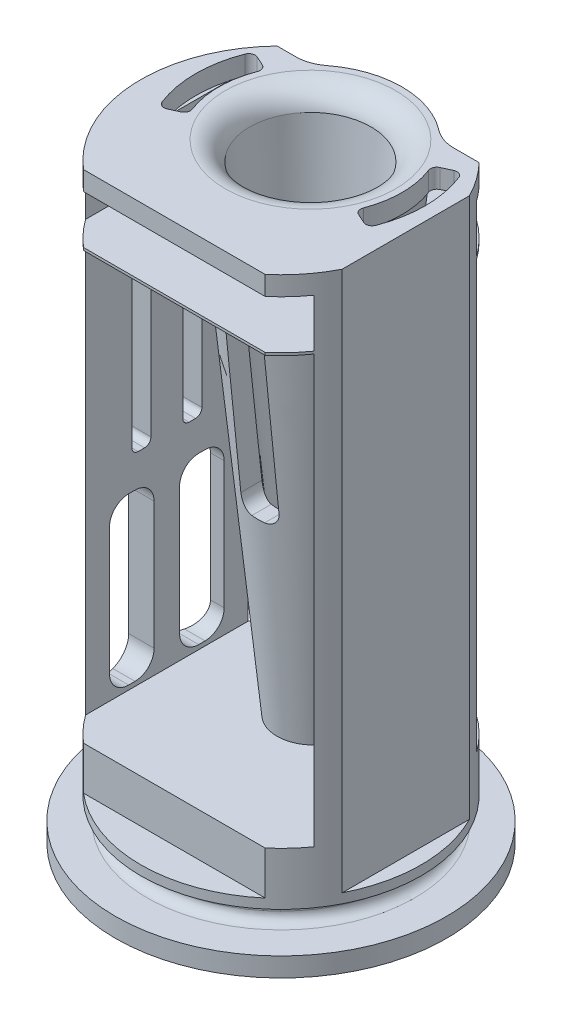
SolidWorks part; units mm, degrees
other "Детальный элемент1"
material "PP Кополимер"
ref_plane "Front Plane" through (0, 0, 0) normal (0, 0, 1) x (1, 0, 0)
ref_plane "Top Plane" through (0, 0, 0) normal (0, 1, 0) x (1, 0, 0)
ref_plane "Right Plane" through (0, 0, 0) normal (1, 0, 0) x (0, 0, -1)
sketch "Эскиз1" plane through (0, 0, 0) normal (0, 1, 0) x (1, 0, 0)
  line L0 (19.6, 9.992) -> (19.6, -9.992)
  line L1 (-14.2632, -16.75) -> (14.2632, -16.75)
  line L2 (-15.8568, 15.25) -> (-12.9239, 15.25)
  line L3 (11.9239, 15.25) -> (15.8568, 15.25)
  line L4 (-0.5, 5.125) -> (-0.5, 23.5612) construction
  line L5 (-0.5, 5.125) -> (-16.8682, 12.625) construction
  line L6 (-14.4479, 11.516) -> (-15.9323, 12.1962)
  line L7 (-14.4479, -1.266) -> (-15.9323, -1.9462)
  line L8 (-0.5, 5.125) -> (-16.8682, -2.375) construction
  line L9 (13.4479, 11.516) -> (14.9323, 12.1962)
  line L10 (13.4479, -1.266) -> (14.9323, -1.9462)
  arc A0 (19.6, 9.992) -> (15.8568, 15.25) centre (0, 0) ccw
  circle A1 centre (-0.5, 5.125) radius 9.5
  arc A2 (8.3046, 16.4881) -> (-9.3046, 16.4881) centre (-0.5, 5.125) ccw
  arc A3 (14.2632, -16.75) -> (19.6, -9.992) centre (0, 0) ccw
  arc A4 (-15.8568, 15.25) -> (-14.2632, -16.75) centre (0, 0) ccw
  arc A5 (-12.9239, 15.25) -> (-9.3046, 16.4881) centre (-12.9239, 21.1592) ccw
  arc A6 (11.9239, 15.25) -> (8.3046, 16.4881) centre (11.9239, 21.1592) cw
  arc A7 (8.3046, 16.4881) -> (-9.3046, 16.4881) centre (-0.5, 5.125) ccw
  arc A9 (-13.9302, 10.2504) -> (-13.9302, -0.0004) centre (-0.5, 5.125) ccw
  arc A10 (-17.2809, 11.6494) -> (-17.2809, -1.3994) centre (-0.5, 5.125) ccw
  arc A11 (-15.9323, -1.9462) -> (-17.2809, -1.3994) centre (-16.3489, -1.0371) cw
  arc A12 (-13.9302, -0.0004) -> (-14.4479, -1.266) centre (-14.8645, -0.3569) cw
  arc A13 (-14.4479, 11.516) -> (-13.9302, 10.2504) centre (-14.8645, 10.6069) cw
  arc A14 (-17.2809, 11.6494) -> (-15.9323, 12.1962) centre (-16.3489, 11.2871) cw
  arc A15 (13.4479, 11.516) -> (12.9302, 10.2504) centre (13.8645, 10.6069) ccw
  arc A16 (16.2809, 11.6494) -> (14.9323, 12.1962) centre (15.3489, 11.2871) ccw
  arc A17 (12.9302, -0.0004) -> (13.4479, -1.266) centre (13.8645, -0.3569) ccw
  arc A18 (14.9323, -1.9462) -> (16.2809, -1.3994) centre (15.3489, -1.0371) ccw
  arc A19 (12.9302, 10.2504) -> (12.9302, -0.0004) centre (-0.5, 5.125) cw
  arc A20 (16.2809, 11.6494) -> (16.2809, -1.3994) centre (-0.5, 5.125) cw
  point P6 (-18.5046, 5.125)
  point P28 (-13.5684, -0.863)
  point P31 (-13.5684, 11.113)
  dimension "D1" = 44
  dimension "D3" = 19
  dimension "D5" = 28.75
  dimension "D9" = 15
  dimension "D10" = 1
  dimension "D2" = 41.6
  dimension "D4" = 10.6
  dimension "D6" = 38.75
  dimension "D7" = 36.25
  dimension "D8" = 32
extrude "основание" add sketch "Эскиз1" along normal blind 3 contours L3 A6 A2 A5 L2 A4 L1 A3 L0 A0 A1 A10 A14 L6 A13 A9 A12 L7 A11 A16 A20 A18 L10 A17 A19 A15 L9 region at (19.0482, 0, 0)
sketch "Эскиз2" plane through (0, 0, 0) normal (0, 1, 0) x (1, 0, 0)
  line L0 (19.6, 9.992) -> (19.6, -9.992) construction
  line L1 (-17.9223, -12.759) -> (17.9223, -12.759) construction
  line L2 (-17.9223, -12.759) -> (-17.9223, 12.759)
  line L3 (-17.9223, 12.759) -> (17.9223, 12.759) construction
  line L4 (17.9223, -12.759) -> (17.9223, 12.759)
  line L5 (-17.9223, -12.759) -> (17.9223, 12.759) construction
  line L6 (-17.9223, 12.759) -> (17.9223, -12.759) construction
  line L7 (19.6, 9.992) -> (19.6, -9.992)
  arc A0 (19.6, 9.992) -> (15.8568, 15.25) centre (0, 0) ccw construction
  arc A1 (-15.8568, 15.25) -> (-14.2632, -16.75) centre (0, 0) ccw construction
  arc A2 (-17.9223, 12.759) -> (-17.9223, -12.759) centre (0, 0) ccw
  arc A3 (14.2632, -16.75) -> (19.6, -9.992) centre (0, 0) ccw construction
  arc A4 (17.9223, -12.759) -> (19.6, -9.992) centre (0, 0) ccw
  arc A5 (19.6, 9.992) -> (17.9223, 12.759) centre (0, 0) ccw
  point P0 (0, 0)
  dimension "D1" = 35.8445
extrude "боковые ребра" add sketch "Эскиз2" against normal blind 75
sketch "Эскиз3" plane through (0, -75, 0) normal (0, -1, 0) x (-1, 0, 0)
  line L0 (14.2632, -16.75) -> (-14.2632, -16.75)
  line L1 (14.2632, -16.75) -> (-14.2632, -16.75) construction
  line L3 (15.8568, 15.25) -> (-7.5223, 20.674)
  line L4 (-19.6, 9.992) -> (-19.6, -9.992)
  line L5 (-19.6, -9.992) -> (-19.6, 9.992) construction
  arc A0 (-7.5223, 20.674) -> (-19.6, 9.992) centre (0, 0) ccw
  arc A1 (-14.2632, -16.75) -> (15.8568, 15.25) centre (0, 0) ccw
  arc A5 (-19.6, -9.992) -> (-14.2632, -16.75) centre (0, 0) ccw
  arc M2 (17.9223, -12.759) -> (17.9223, 12.759) centre (0, 0) ccw
  line M3 (17.9223, 12.759) -> (17.9223, -12.759)
  dimension "D1" = 24
extrude "примыкание ручки" add sketch "Эскиз3" along normal blind 2.8 contours L0 A1 L3 A0 M3 | M3 M2 region at (0.7797, -75, -0.6462) region at (-19.5671, -75, 0)
sketch "Эскиз4" plane through (-17.9223, 0, 0) normal (1, 0, 0) x (0, 0, -1)
  line L0 (0, 0) -> (0, -77.8) construction
  line L1 (2, -51.3) -> (2, -71.3)
  line L2 (-16.75, -77.8) -> (15.25, -77.8) construction
  line L3 (6, -74.3) -> (5, -74.3)
  line L4 (9, -71.3) -> (9, -51.3)
  line L5 (6, -48.3) -> (5, -48.3)
  line L6 (-9, -71.3) -> (-9, -51.3)
  line L7 (9, -74.3) -> (-9, -48.3) construction
  line L8 (9, -48.3) -> (-9, -74.3) construction
  line L14 (9.992, -77.8) -> (-9.992, -77.8) construction
  line L15 (5.5, -43.3) -> (2.5, -8.3) construction
  line L21 (-4.5, -8.3) -> (-3.5, -8.3)
  line L22 (-5.5, -9.3) -> (-5.5, -42.3)
  line L45 (-4.5, -43.3) -> (-3.5, -43.3)
  line L46 (-2.5, -9.3) -> (-2.5, -42.3)
  line L47 (-5.5, -8.3) -> (-2.5, -43.3) construction
  line L48 (-5.5, -43.3) -> (-2.5, -8.3) construction
  line L65 (5.5, -8.3) -> (2.5, -43.3) construction
  line L66 (2.5, -9.3) -> (2.5, -42.3)
  line L67 (4.5, -43.3) -> (3.5, -43.3)
  line L68 (5.5, -9.3) -> (5.5, -42.3)
  line L85 (4.5, -8.3) -> (3.5, -8.3)
  line L86 (-2, -51.3) -> (-2, -71.3)
  line L87 (-5, -48.3) -> (-6, -48.3)
  line L88 (-5, -74.3) -> (-6, -74.3)
  arc A0 (6, -74.3) -> (9, -71.3) centre (6, -71.3) ccw
  arc A1 (-6, -74.3) -> (-9, -71.3) centre (-6, -71.3) cw
  arc A2 (-6, -48.3) -> (-9, -51.3) centre (-6, -51.3) ccw
  arc A3 (9, -51.3) -> (6, -48.3) centre (6, -51.3) ccw
  arc A4 (-3.5, -43.3) -> (-2.5, -42.3) centre (-3.5, -42.3) ccw
  arc A5 (-4.5, -43.3) -> (-5.5, -42.3) centre (-4.5, -42.3) cw
  arc A6 (-3.5, -8.3) -> (-2.5, -9.3) centre (-3.5, -9.3) cw
  arc A7 (-4.5, -8.3) -> (-5.5, -9.3) centre (-4.5, -9.3) ccw
  arc A8 (4.5, -8.3) -> (5.5, -9.3) centre (4.5, -9.3) cw
  arc A9 (3.5, -8.3) -> (2.5, -9.3) centre (3.5, -9.3) ccw
  arc A10 (4.5, -43.3) -> (5.5, -42.3) centre (4.5, -42.3) ccw
  arc A11 (3.5, -43.3) -> (2.5, -42.3) centre (3.5, -42.3) cw
  arc A12 (5, -74.3) -> (2, -71.3) centre (5, -71.3) cw
  arc A13 (5, -48.3) -> (2, -51.3) centre (5, -51.3) ccw
  arc A14 (-5, -74.3) -> (-2, -71.3) centre (-5, -71.3) ccw
  arc A15 (-5, -48.3) -> (-2, -51.3) centre (-5, -51.3) cw
  point P5 (0, -61.3)
  point P28 (-4, -25.8)
  point P57 (4, -25.8)
  dimension "D4" = 3
  dimension "D8" = 1
  dimension "D11" = 3
  dimension "D1" = 18
  dimension "D2" = 26
  dimension "D3" = 3.5
  dimension "D5" = 5
  dimension "D6" = 5
  dimension "D7" = 3
  dimension "D9" = 35
  dimension "D10" = 4
extrude "перфорация боковых стенок" cut sketch "Эскиз4" against normal through all
sketch "Эскиз6" plane through (0, 0, 0) normal (0, -1, 0) x (-1, 0, 0)
  point P0 (0.5, 5.125)
ref_plane "Плоскость1" through (0, 0, -5.125) normal (0, 0, -1) x (-1, 0, 0)
sketch "Эскиз7" plane through (0, 0, -5.125) normal (0, 0, -1) x (-1, 0, 0)
  line L0 (0, 0) -> (0, -75) construction
  line L1 (15.8568, -75) -> (-7.5223, -75) construction
  line L2 (2.736, -75) -> (10, 0)
  line L3 (-8.3046, 0) -> (9.3046, 0) construction
  line L4 (10, 0) -> (13.014, 0)
  line L6 (13.014, 0) -> (5.75, -75)
  line L7 (5.75, -75) -> (2.736, -75)
  line L9 (-9, 0) -> (10, 0) construction
  dimension "D1" = 11.5
  dimension "D2" = 3
revolve "внутрении конус" add sketch "Эскиз7" angle 360 about L0
sketch "Эскиз8" plane through (0, 0, -5.125) normal (0, 0, -1) x (-1, 0, 0)
  line L0 (-3, -12) -> (-3, -42)
  line L2 (-8.3046, 0) -> (9.3046, 0) construction
  line L3 (-1, -10) -> (1, -10)
  line L7 (3, -12) -> (3, -42)
  line L23 (-1, -44) -> (1, -44)
  arc A0 (1, -44) -> (3, -42) centre (1, -42) ccw
  arc A1 (-3, -42) -> (-1, -44) centre (-1, -42) ccw
  arc A2 (-1, -10) -> (-3, -12) centre (-1, -12) ccw
  arc A3 (1, -10) -> (3, -12) centre (1, -12) cw
  point P5 (0, -13)
  dimension "D1" = 2
  dimension "D2" = 10
extrude "перфорация конуса" cut sketch "Эскиз8" against normal through all both and the other way through all
fillet "Скруг основ конуса" radius 4 1 edges at (-0.5, 3, 4.375)
sketch "Эскиз9" plane through (0, -77.8, 0) normal (0, -1, 0) x (1, 0, 0)
  line L3 (19.6, -9.992) -> (19.6, 9.992)
  line L4 (14.2632, 16.75) -> (-14.2632, 16.75)
  line L5 (-15.8568, -15.25) -> (7.5223, -20.674)
  line L6 (19.6, -9.992) -> (19.6, 9.992)
  line L7 (14.2632, 16.75) -> (-14.2632, 16.75)
  line L8 (-15.8568, -15.25) -> (7.5223, -20.674)
  circle A0 centre (0, 0) radius 14.4801
  arc A4 (19.6, 9.992) -> (14.2632, 16.75) centre (0, 0) ccw
  arc A5 (-14.2632, 16.75) -> (-15.8568, -15.25) centre (0, 0) ccw
  arc A6 (7.5223, -20.674) -> (19.6, -9.992) centre (0, 0) ccw
  arc A7 (19.6, 9.992) -> (14.2632, 16.75) centre (0, 0) ccw
  arc A8 (-14.2632, 16.75) -> (-15.8568, -15.25) centre (0, 0) ccw
  arc A9 (7.5223, -20.674) -> (19.6, -9.992) centre (0, 0) ccw
  line M1 (19.6, -9.992) -> (19.6, 9.992)
  arc M2 (19.6, 9.992) -> (14.2632, 16.75) centre (0, 0) ccw
  line M3 (14.2632, 16.75) -> (-14.2632, 16.75)
  arc M4 (-14.2632, 16.75) -> (-15.8568, -15.25) centre (0, 0) ccw
  line M5 (-15.8568, -15.25) -> (7.5223, -20.674)
  arc M6 (7.5223, -20.674) -> (19.6, -9.992) centre (0, 0) ccw
  dimension "D1" = 0
extrude "шейка ручки" add sketch "Эскиз9" along normal blind 4 contours A0 | A0 M6 M1 M2 M3 M4 M5 region at (14.2043, -77.8, -16.0602) region at (0, -77.8, 0)
sketch "Эскиз10" plane through (0, -81.8, 0) normal (0, -1, 0) x (1, 0, 0)
  circle A0 centre (0, 0) radius 22
  dimension "D1" = 44
extrude "бортик перед прокладкой" add sketch "Эскиз10" along normal blind 1.5
sketch "Эскиз11" plane through (0, -83.3, 0) normal (0, -1, 0) x (1, 0, 0)
  circle A0 centre (0, 0) radius 19.5
  dimension "D1" = 39
extrude "прокладка паз" add sketch "Эскиз11" along normal blind 3.5
sketch "Эскиз12" plane through (0, -86.8, 0) normal (0, -1, 0) x (-1, 0, 0)
  circle A0 centre (0, 0) radius 26
  dimension "D1" = 52
extrude "бортик после прокладки" add sketch "Эскиз12" along normal blind 3
sketch "Эскиз13" plane through (0, -89.8, 0) normal (0, -1, 0) x (1, 0, 0)
  circle A0 centre (0, 0) radius 14
  dimension "D1" = 28
extrude "вырез под внеш ручку" cut sketch "Эскиз13" against normal blind 12
sketch "Эскиз15" plane through (0, -89.8, 0) normal (0, -1, 0) x (1, 0, 0)
  circle A0 centre (0, 0) radius 19
  dimension "D1" = 38
extrude "Вырез-Вытянуть1" [suppressed] cut sketch "Эскиз15" against normal blind 2
sketch "Эскиз16" plane through (0, -89.8, 0) normal (0, -1, 0) x (1, 0, 0)
  circle A0 centre (0, 0) radius 16
  circle A1 centre (0, 0) radius 13
  dimension "D1" = 32
  dimension "D2" = 26
extrude "выступ под упор винтовой крышки" add sketch "Эскиз16" against normal blind 3
fillet "Скругление4" radius 1.5 2 edges at (0, -83.3, -19.5) (0, -86.8, -19.5)
fillet "Скругление3" [suppressed] radius 2
chamfer "Фаска3" [suppressed] distance 4 angle 45
ref_plane "Плоскость2" through (0, -8, 0) normal (0, -1, 0) x (-1, 0, 0)
sketch "Эскиз17" plane through (0, -8, 0) normal (0, -1, 0) x (-1, 0, 0)
  line L0 (-17.9223, 12.759) -> (-17.9223, -12.759)
  line L1 (-14.2632, -16.75) -> (14.2632, -16.75)
  line L2 (17.9223, -12.759) -> (17.9223, 12.759)
  line L3 (15.8568, 15.25) -> (-7.5223, 20.674)
  arc A0 (-17.9223, 12.759) -> (-7.5223, 20.674) centre (0, 0) cw
  arc A1 (-17.9223, -12.759) -> (-14.2632, -16.75) centre (0, 0) ccw
  arc A2 (14.2632, -16.75) -> (17.9223, -12.759) centre (0, 0) ccw
  circle A3 centre (0, 5.125) radius 12.0139
  arc A4 (17.9223, 12.759) -> (15.8568, 15.25) centre (0, 0) ccw
extrude "Бобышка-Вытянуть2" add sketch "Эскиз17" against normal blind 0.4
chamfer "фаска под ручку " [suppressed] distance 8 distance2 5
